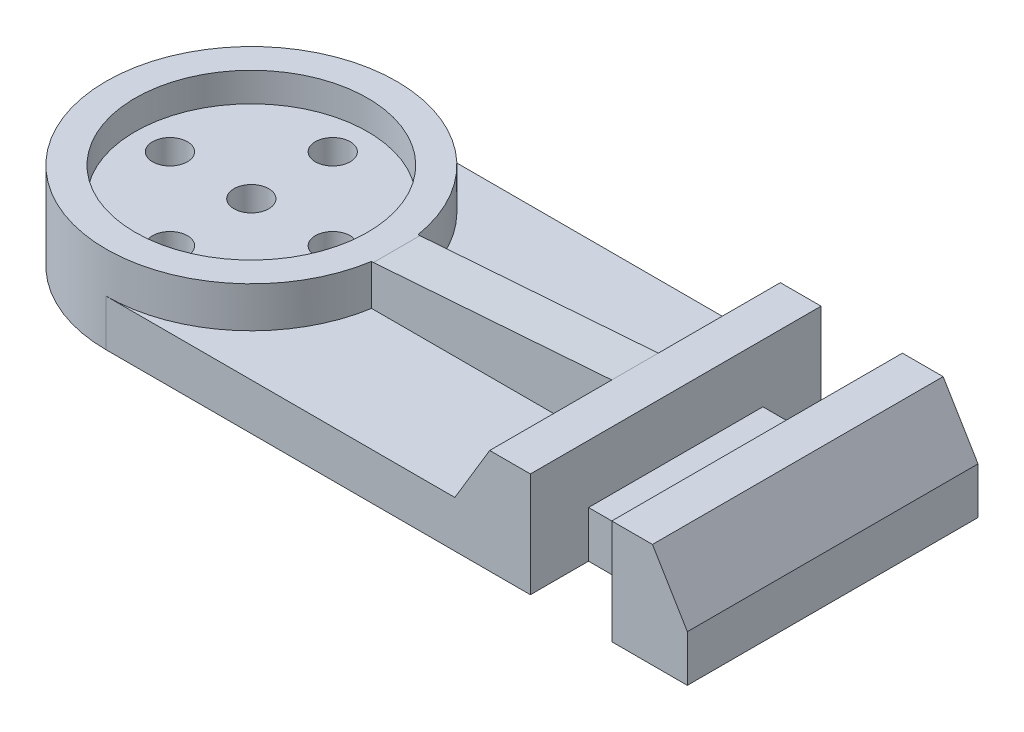
SolidWorks part; units mm, degrees
material "ABS"
ref_plane "前视基准面" through (0, 0, 0) normal (0, 0, 1) x (1, 0, 0)
ref_plane "上视基准面" through (0, 0, 0) normal (0, 1, 0) x (1, 0, 0)
ref_plane "右视基准面" through (0, 0, 0) normal (1, 0, 0) x (0, 0, -1)
sketch "草图1" plane through (0, 0, 0) normal (0, 1, 0) x (1, 0, 0)
  line L0 (0, 12.5) -> (50, 12.5)
  line L1 (0, -12.5) -> (50, -12.5)
  line L2 (50, 12.5) -> (50, -12.5)
  circle A0 centre (0, 0) radius 12.5
  dimension "D1" = 25
  dimension "D2" = 50
extrude "凸台-拉伸1" add sketch "草图1" along normal blind 4 contours A0 | A0 L1 L2 L0 region at (29.8119, 0, 0) region at (0, 0, 0)
sketch "草图2" plane through (0, 4, 0) normal (0, 1, 0) x (1, 0, 0)
  circle A0 centre (0, 0) radius 12.5
  circle A1 centre (0, 0) radius 10
  dimension "D1" = 25
  dimension "D2" = 20
extrude "凸台-拉伸2" add sketch "草图2" along normal blind 3.5
sketch "草图3" plane through (0, 0, 0) normal (0, -1, 0) x (1, 0, 0)
  line L0 (0, 16.9978) -> (0, -21.3221) construction
  line L1 (-30.6103, 0) -> (69.188, 0) construction
  circle A0 centre (0, 0) radius 1.5
  circle A1 centre (0, 7) radius 1.5
  circle A2 centre (7, 0) radius 1.5
  circle A3 centre (0, -7) radius 1.5
  circle A4 centre (-7, 0) radius 1.5
  circle A5 centre (40, 0) radius 1.5
  dimension "D1" = 3
  dimension "D2" = 3
  dimension "D5" = 3
  dimension "D3" = 7
  dimension "D6" = 40
  dimension "D4" = 4
extrude "切除-拉伸1" cut sketch "草图3" against normal through all
sketch "草图4" plane through (0, 0, 12.5) normal (0, 0, 1) x (1, 0, 0)
  line L0 (40, 14.1176) -> (40, -14.2645) construction
  line L2 (50, 4) -> (47, 9)
  line L3 (47, 9) -> (33, 9)
  line L4 (0, 4) -> (50, 4) construction
  line L5 (30, 4) -> (33, 9)
  line L6 (30, 4) -> (50, 4)
  point P11 (40, 9)
  dimension "D1" = 40
  dimension "D2" = 7
  dimension "D3" = 5
extrude "凸台-拉伸3" add sketch "草图4" against normal up to surface (25 mm away) up to face at (25, 2, -12.5)
sketch "草图5" plane through (0, 0, 12.5) normal (0, 0, 1) x (1, 0, 0)
  line L0 (40, 19.3346) -> (40, -11.3346) construction
  line L1 (36.5, 9) -> (43.5, 9)
  line L2 (47, 9) -> (33, 9) construction
  line L3 (43.5, 9) -> (43.5, 4)
  line L4 (43.5, 4) -> (36.5, 4)
  line L5 (36.5, 9) -> (36.5, 4)
  point P10 (40, 4)
  point P11 (40, 9)
  dimension "D1" = 40
  dimension "D2" = 3.5
  dimension "D3" = 5
extrude "切除-拉伸2" cut sketch "草图5" against normal through all
sketch "草图6" plane through (0, 4, 0) normal (0, 1, 0) x (1, 0, 0)
  line L0 (36.5, -12.5) -> (43.5, -12.5)
  line L1 (43.5, -12.5) -> (43.5, -7.5)
  line L2 (43.5, -7.5) -> (36.5, -7.5)
  line L3 (36.5, 12.5) -> (36.5, -12.5) construction
  line L4 (36.5, -7.5) -> (36.5, -12.5)
  line L5 (-16.7425, 0) -> (62.5585, 0) construction
  line L6 (36.5, 12.5) -> (43.5, 12.5)
  line L7 (36.5, 7.5) -> (36.5, 12.5)
  line L8 (43.5, 12.5) -> (43.5, 7.5)
  line L9 (43.5, 7.5) -> (36.5, 7.5)
  dimension "D1" = 5
extrude "切除-拉伸3" cut sketch "草图6" against normal through all
sketch "草图7" plane through (0, 0, 0) normal (0, 0, 1) x (1, 0, 0)
  line L4 (30, 4) -> (33, 9)
  line L5 (33, 9) -> (12.5, 7.5)
  line L9 (30, 4) -> (10.3514, 4)
  line L10 (0, 4) -> (30, 4) construction
  line L11 (10.3514, 4) -> (10.3514, 7.5)
  line L12 (12.5, 7.5) -> (-12.5, 7.5) construction
  line L13 (10.3514, 7.5) -> (12.5, 7.5)
extrude "凸台-拉伸6" add sketch "草图7" along normal mid plane 4
sketch "草图8" plane through (0, 4, 0) normal (0, 1, 0) x (1, 0, 0)
  circle A0 centre (0, 0) radius 10
  circle A1 centre (0, 0) radius 1.5
  circle A2 centre (0, 7) radius 1.5
  circle A3 centre (7, 0) radius 1.5
  circle A4 centre (0, -7) radius 1.5
  circle A5 centre (-7, 0) radius 1.5
extrude "凸台-拉伸7" add sketch "草图8" along normal blind 1
